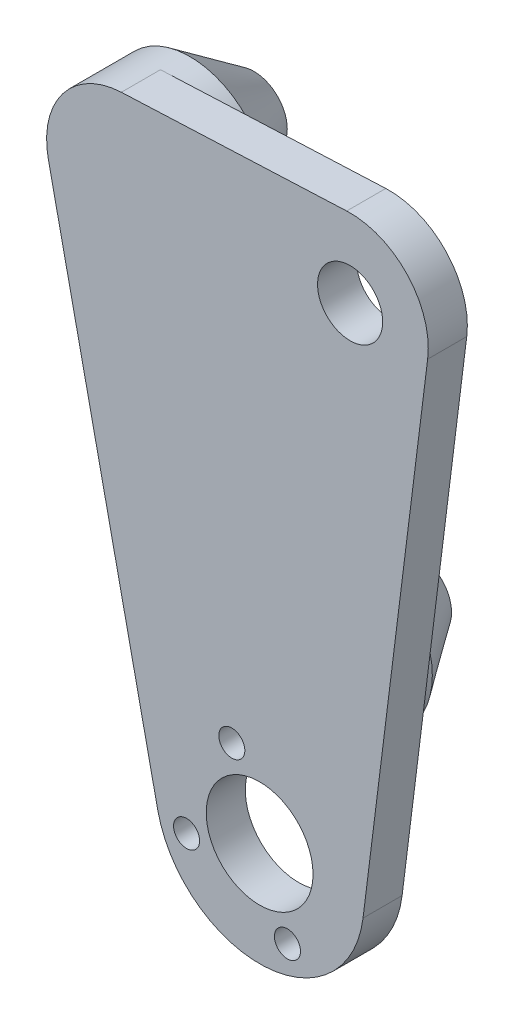
SolidWorks part; units mm, degrees
note: '?' marks a value the reader was unsure of. The reader was unsure of these and kept them because the rebuilt part matched: shared geometry of "Sketch1<3>", "Sketch1<4>", "Sketch1<5>".
ref_plane "Front Plane" through (0, 0, 0) normal (0, 0, 1) x (1, 0, 0)
ref_plane "Top Plane" through (0, 0, 0) normal (0, 1, 0) x (1, 0, 0)
ref_plane "Right Plane" through (0, 0, 0) normal (1, 0, 0) x (0, 0, -1)
sketch "Sketch1" plane through (0, 0, 0) normal (0, 0, 1) x (1, 0, 0)
  line L0 (0, 0) -> (83.6671, 0) construction
  line L1 (0, 0) -> (4.1676, 23.6354) construction
  line L2 (0, 0) -> (-10.3528, 38.637) construction
  line L3 (-7.8213, -1.6816) -> (-16.2187, 37.3758)
  line L4 (-6.0415, 42.8099) -> (8.4788, 27.8083)
  line L5 (10.1427, 23.0895) -> (7.9668, -0.7278)
  circle A0 centre (0, 0) radius 8
  arc A1 (10.1427, 23.0895) -> (7.3532, 28.7199) centre (4.1676, 23.6354) ccw
  circle A2 centre (-10.3528, 38.637) radius 6
  circle A3 centre (2.2574, 12.8025) radius 4 construction
  circle A5 centre (-10.3528, 38.637) radius 4 construction
  circle A6 centre (2.2574, 12.8025) radius 6
  circle A7 centre (2.1676, 25.7017) radius 6
  circle A8 centre (2.1676, 25.7017) radius 4 construction
  dimension "D1" = 24
  dimension "D3" = 16
  dimension "D4" = 40
  dimension "D6" = 12
  dimension "D7" = 12
  dimension "D8" = 8
  dimension "D11" = 8
  dimension "D12" = 8
  dimension "D13" = 20.4954
  dimension "D15" = 12
  dimension "D16" = 12
  dimension "D2" = 80
  dimension "D5" = 105
  dimension "D9" = 11
  dimension "D10" = 13
  dimension "D14" = 29.4899
  dimension "D17" = 2
extrude "Boss-Extrude1" add sketch "Sketch1" along normal blind 3 contours A2 L3 A0 L5 A1 L4 | A1 | A2 | A0 | A6 A0 L5 A1 | A7 | A0 A6 | A0 A6
sketch "Sketch10" plane through (0, 0, 0) normal (0, 0, 1) x (1, 0, 0)
  line L0 (0, 0) -> (83.6671, 0) construction
  line L1 (0, 0) -> (6.9459, 39.3923) construction
  line L2 (-7.7991, 1.7814) -> (1.0966, 40.7283)
  line L3 (12.8995, 38.6472) -> (7.9381, -0.9935)
  line L4 (6.6842, 45.3866) -> (-10.6145, 44.6313)
  line L5 (-10.6145, 44.6313) -> (-7.7991, 1.7814)
  circle A0 centre (6.9459, 39.3923) radius 6
  circle A1 centre (6.9459, 39.3923) radius 4 construction
  circle A2 centre (0, 0) radius 8
  circle A3 centre (-10.3528, 38.637) radius 6 construction
  dimension "D3" = 8
  dimension "D4" = 12
  dimension "D1" = 40
  dimension "D2" = 80
extrude "Boss-Extrude5" add sketch "Sketch10" along normal blind 3 contours A2 L3 A0 L2 | A0 L4 L5 L2
sketch "Sketch3" plane through (0, 0, 3) normal (0, 0, 1) x (1, 0, 0)
  circle A0 centre (0, 0) radius 4.1
  dimension "D1" = 8.2
extrude "Cut-Extrude1" cut sketch "Sketch3" against normal blind 50
ref_axis "Axis1" through (2.1676, 25.7017, 0) along (0, 0, 1)?
ref_axis "Axis2" through (-10.3528, 38.637, 0) along (0, 0, 1)?
ref_axis "Axis3" through (0, 0, 0) along (0, 0, 1)?
ref_axis "Axis4" through (2.2574, 12.8025, 0) along (0, 0, 1)?
sketch "Sketch5" plane through (0, 0, 3) normal (0, 0, 1) x (1, 0, 0)
  line L0 (0, 0) -> (83.6671, 0) construction
  line L1 (0, 0) -> (4.1676, 23.6354) construction
  line L2 (0, 0) -> (-10.3528, 38.637) construction
  line L3 (-7.8213, -1.6816) -> (-16.2187, 37.3758)
  line L4 (-6.0415, 42.8099) -> (8.4788, 27.8083)
  line L5 (10.1427, 23.0895) -> (7.9668, -0.7278)
  circle A0 centre (0, 0) radius 8
  circle A1 centre (4.1676, 23.6354) radius 6
  circle A2 centre (-10.3528, 38.637) radius 6
  circle A3 centre (2.2574, 12.8025) radius 4 construction
  circle A4 centre (4.1676, 23.6354) radius 4 construction
  circle A5 centre (-10.3528, 38.637) radius 4 construction
  circle A6 centre (2.2574, 12.8025) radius 6
  dimension "D1" = 24
  dimension "D3" = 16
  dimension "D4" = 40
  dimension "D6" = 12
  dimension "D7" = 12
  dimension "D8" = 8
  dimension "D11" = 8
  dimension "D12" = 8
  dimension "D13" = 20.4954
  dimension "D2" = 80
  dimension "D5" = 105
  dimension "D9" = 11
  dimension "D10" = 13
  dimension "D14" = 29.4899
ref_plane "Plane1" through (-10.3528, 0, 0) normal (1, 0, 0) x (0, 0, -1)
ref_plane "Plane2" through (2.1676, 0, 0) normal (1, 0, 0) x (0, 0, -1)
ref_plane "Plane3" through (2.2574, 0, 0) normal (1, 0, 0) x (0, 0, -1)
extrude "Boss-Extrude2" add sketch "Sketch1<3>" against normal blind 7 contours A2
sketch "Sketch1<3>" plane through (0, 0, 0) normal (0, 0, 1) x (1, 0, 0) same geometry as "Sketch1"
extrude "Boss-Extrude3" add sketch "Sketch1<4>" against normal blind 7 contours A7
sketch "Sketch1<4>" plane through (0, 0, 0) normal (0, 0, 1) x (1, 0, 0) same geometry as "Sketch1"
extrude "Boss-Extrude6" add sketch "Sketch1<5>" against normal blind 7 contours A6
sketch "Sketch1<5>" plane through (0, 0, 0) normal (0, 0, 1) x (1, 0, 0) same geometry as "Sketch1"
ref_point "Point6"
ref_point "Point8"
ref_point "Point10"
sketch "Sketch6" plane through (-10.3528, 0, 0) normal (1, 0, 0) x (0, 0, -1)
  line L0 (7, 38.637) -> (10, 38.637) construction
  line L1 (0, 38.637) -> (-20.0979, 38.637) construction
  line L2 (10, 42.637) -> (10, 34.637)
  circle A0 centre (10, 38.637) radius 4
  dimension "D2" = 8
  dimension "D1" = 3
revolve "Cut-Revolve1" cut sketch "Sketch6" angle 360 about L2
sketch "Sketch7" plane through (2.1676, 0, 0) normal (1, 0, 0) x (0, 0, -1)
  line L0 (7, 25.7017) -> (10, 25.7017) construction
  line L1 (0, 25.7017) -> (-20.0979, 25.7017) construction
  line L2 (10, 29.7017) -> (10, 21.7017)
  circle A0 centre (10, 25.7017) radius 4
  dimension "D2" = 8
  dimension "D1" = 3
revolve "Cut-Revolve2" cut sketch "Sketch7" angle 360 about L2
sketch "Sketch14" plane through (2.2574, 0, 0) normal (1, 0, 0) x (0, 0, -1)
  line L0 (7, 12.8025) -> (10, 12.8025) construction
  line L1 (0, 12.8025) -> (-20.0979, 12.8025) construction
  line L2 (10, 16.8025) -> (10, 8.8025)
  circle A0 centre (10, 12.8025) radius 4
  dimension "D2" = 8
  dimension "D1" = 3
revolve "Cut-Revolve3" cut sketch "Sketch14" angle 360 about L2
chamfer "Chamfer8" distance 5 angle 35 3 edges at (-4.3528, 38.637, -7) (8.1676, 25.7017, -7) (8.2574, 12.8025, -7) first distance on face at (-11.8847, 39.8203, 1.5) first distance on face at (8.1676, 25.7017, -7) first distance on face at (8.2574, 12.8025, -7)
sketch "Sketch9" plane through (0, 0, 3) normal (0, 0, 1) x (1, 0, 0)
  line L0 (0, 0) -> (83.6671, 0) construction
  line L1 (0, 0) -> (-2.1355, 5.6071) construction
  circle A0 centre (-2.1355, 5.6071) radius 1
  circle A4 centre (5.6071, 2.1355) radius 1
  circle A5 centre (2.1355, -5.6071) radius 1
  circle A6 centre (-5.6071, -2.1355) radius 1
  point P15 (0, 0)
  point P16 (0, 0)
  dimension "D1" = 6
  dimension "D3" = 2
  dimension "D2" = 110.85
  dimension "D4" = 4
extrude "Cut-Extrude3" cut sketch "Sketch9" against normal blind 3 contours A6 | A0 | A5
sketch "Sketch13" plane through (0, 0, 3) normal (0, 0, 1) x (1, 0, 0)
  circle A0 centre (6.9459, 39.3923) radius 2.5
  dimension "D1" = 5
extrude "Cut-Extrude4" cut sketch "Sketch13" against normal blind 3 contours A0
